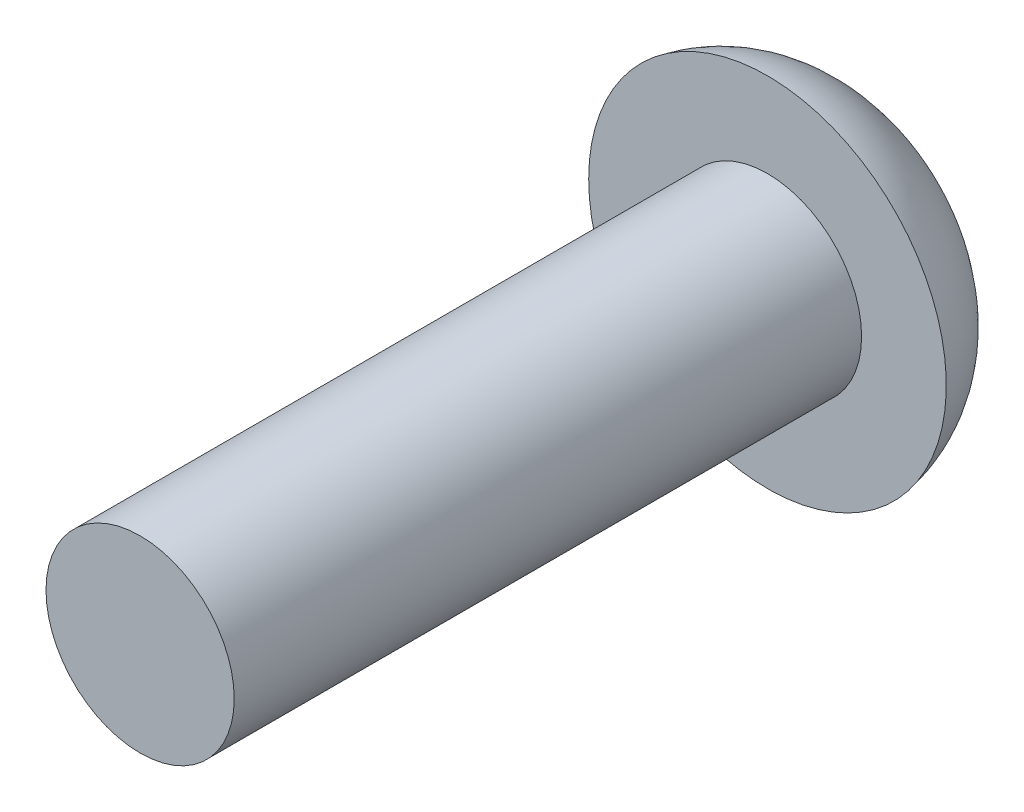
SolidWorks part; units mm, degrees
ref_plane "前视基准面" through (0, 0, 0) normal (0, 0, 1) x (1, 0, 0)
ref_plane "上视基准面" through (0, 0, 0) normal (0, 1, 0) x (1, 0, 0)
ref_plane "右视基准面" through (0, 0, 0) normal (1, 0, 0) x (0, 0, -1)
sketch "草图1" plane through (0, 0, 0) normal (0, 0, 1) x (1, 0, 0)
  circle A0 centre (0, 0) radius 1.5
extrude "凸台-拉伸1" add sketch "草图1" along normal blind 10
sketch "草图2" plane through (0, 0, 0) normal (0, 0, -1) x (-1, 0, 0)
  circle A0 centre (0, 0) radius 2.85
extrude "凸台-拉伸2" add sketch "草图2" along normal blind 1.65
fillet "圆角1" radius 2 1 edges at (-2.85, 0, -1.65)
sketch "草图3" plane through (0, 0, 0) normal (0, 0, 1) x (1, 0, 0)
  circle A0 centre (0, 0) radius 1.55
  dimension "D1" = 3.1
